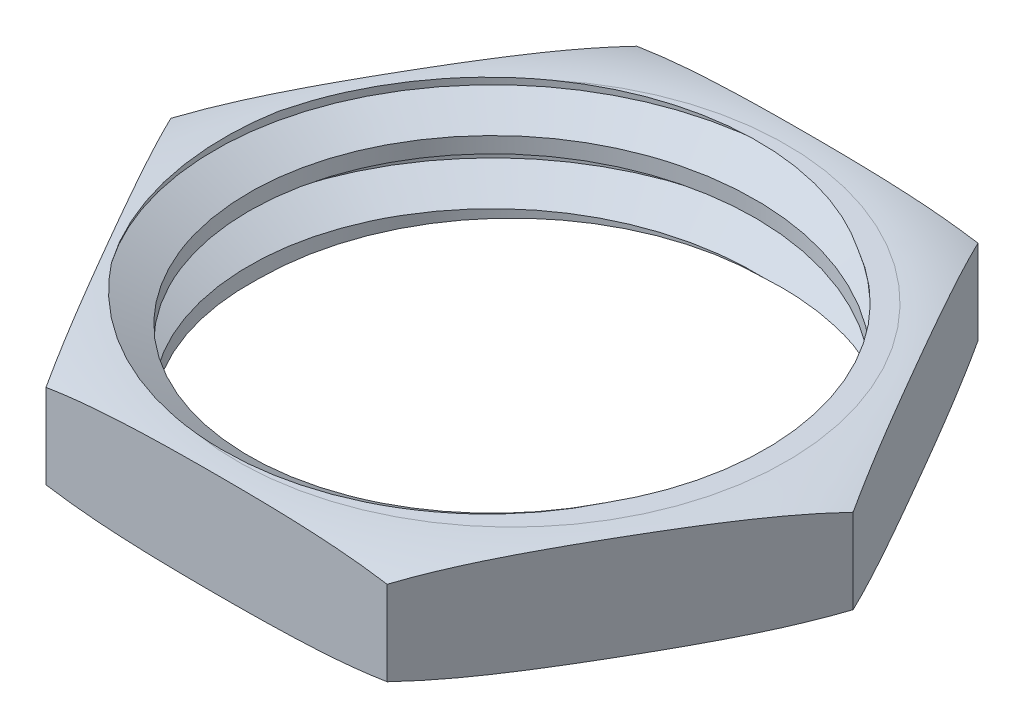
SolidWorks part; units mm, degrees
ref_plane "Front Plane" through (0, 0, 0) normal (0, 0, 1) x (1, 0, 0)
ref_plane "Top Plane" through (0, 0, 0) normal (0, 1, 0) x (1, 0, 0)
ref_plane "Right Plane" through (0, 0, 0) normal (1, 0, 0) x (0, 0, -1)
sketch "Sketch9" plane through (0, 0, 0) normal (0, 0, 1) x (1, 0, 0)
  line L0 (0, 0) -> (0, 2.1443) construction
  line L1 (6, 2.5) -> (6, 0)
  line L2 (6, 2.5) -> (6.5, 2.5)
  line L3 (8.08, 2.25) -> (8.08, 0.25)
  line L4 (6, 0) -> (6.5, 0)
  arc A0 (6.5, 2.5) -> (8.08, 2.25) centre (6.5, -2.6178) cw
  arc A1 (6.5, 0) -> (8.08, 0.25) centre (6.5, 5.1178) ccw
  point P11 (6.5978, 0)
  point P12 (8.08, 0.25)
  point P13 (6.5, 2.3441)
  dimension "D2" = 8.08
  dimension "D5" = 2.5
  dimension "D1" = 6
  dimension "D3" = 0.5
  dimension "D4" = 0.25
revolve "Revolve1" add sketch "Sketch9" angle 360 about L0
sketch "Sketch10" plane through (0, 2.5, 0) normal (0, 1, 0) x (1, 0, 0)
  line L1 (4.04, 6.9975) -> (-4.04, 6.9975)
  line L2 (-4.04, 6.9975) -> (-8.08, 0)
  line L3 (-8.08, 0) -> (-4.04, -6.9975)
  line L4 (-4.04, -6.9975) -> (4.04, -6.9975)
  line L5 (4.04, -6.9975) -> (8.08, 0)
  line L6 (8.08, 0) -> (4.04, 6.9975)
  circle A0 centre (0, 0) radius 6.9975 construction
  circle A1 centre (0, 0) radius 8.08
  circle A2 centre (0, 0) radius 8.08 construction
  point P10 (3.5398, -6.1311)
extrude "Cut-Extrude1" cut sketch "Sketch10" against normal through all both and the other way through all contours L5 A1 | L6 A1 | L4 A1 | L3 A1 | L2 A1 | L1 A1 region at (6.4372, 2.5, -3.7165) region at (0, 2.5, -7.4331) region at (-6.4372, 2.5, -3.7165) region at (6.4372, 2.5, 3.7165) region at (-6.4372, 2.5, 3.7165) region at (0, 2.5, 7.4331)
thread "Thread1" pitch 1.5 method cut profile "Thread Profile1" start angle 0, offset 2, length 10, pitch 1.5, diameter 12
ref_plane "Plane1" through (-6, 4.5, 0) normal (0, 0, 1) x (-1, 0, 0)
sketch "Thread Profile1" plane through (-6, 4.5, 0) normal (0, 0, 1) x (-1, 0, 0)
  line L0 (0, 0) -> (0, 1.5) construction
  line L1 (0, 0) -> (0.8119, 0.4687)
  line L2 (0.8119, 0.4687) -> (0.8119, 0.6562)
  line L3 (0.8119, 0.6562) -> (0, 1.125)
  line L4 (0.8119, 0.5625) -> (0, 0.5625) construction
  line L11 (0, 0) -> (0, 1.125)
  point P2 (0, 0)
  dimension "Pitch" = 1.5
  dimension "Profile_Angle" = 60
  dimension "Profile_Land" = 0.1875
  dimension "Profile_Height" = 0.8119
